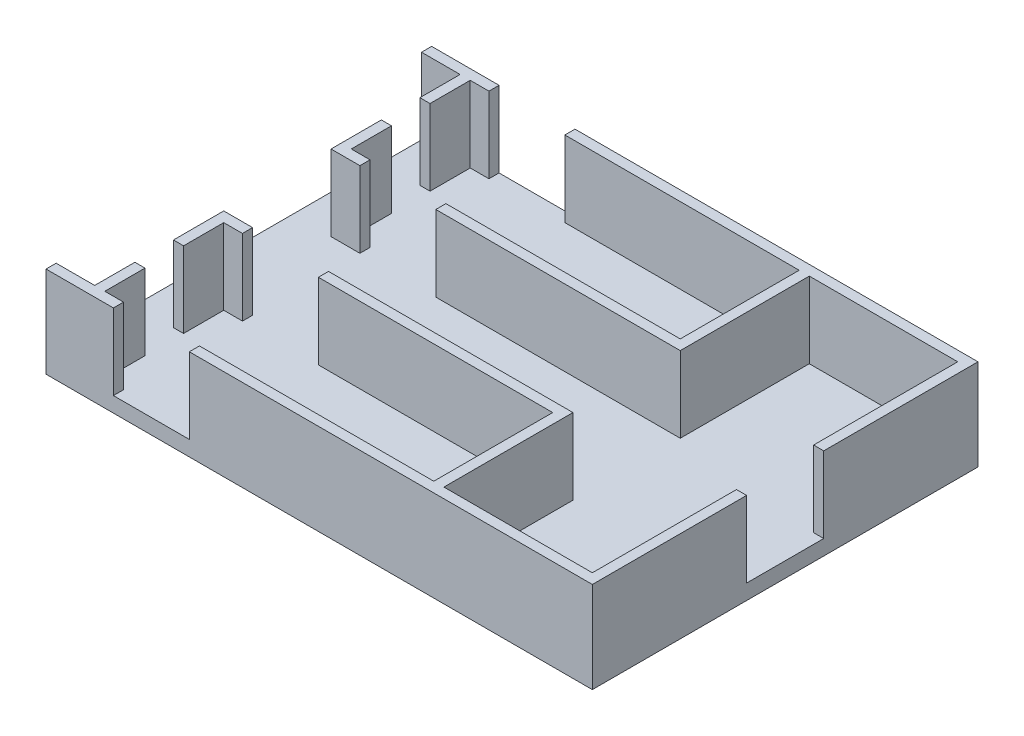
SolidWorks part; units mm, degrees
ref_plane "Front Plane" through (0, 0, 0) normal (0, 0, 1) x (1, 0, 0)
ref_plane "Top Plane" through (0, 0, 0) normal (0, 1, 0) x (1, 0, 0)
ref_plane "Right Plane" through (0, 0, 0) normal (1, 0, 0) x (0, 0, -1)
sketch "Sketch1" plane through (0, 0, 0) normal (0, 1, 0) x (1, 0, 0)
  line L1 (-53.975, 38.1) -> (53.975, 38.1)
  line L2 (-53.975, 38.1) -> (-53.975, -38.1)
  line L3 (-53.975, -38.1) -> (53.975, -38.1)
  line L4 (53.975, 38.1) -> (53.975, -38.1)
  line L5 (-53.975, 38.1) -> (53.975, -38.1) construction
  line L6 (-53.975, -38.1) -> (53.975, 38.1) construction
  point P0 (0, 0)
  dimension "D1" = 76.2
  dimension "D2" = 107.95
extrude "Boss-Extrude1" add sketch "Sketch1" along normal blind 3
sketch "Sketch2" plane through (0, 3, 0) normal (0, 1, 0) x (1, 0, 0)
  line L0 (-51.975, 36.1) -> (-53.975, 36.1)
  line L1 (-53.975, 38.1) -> (53.975, 38.1)
  line L2 (-53.975, 38.1) -> (-53.975, -38.1)
  line L3 (-53.975, -38.1) -> (53.975, -38.1)
  line L4 (53.975, 38.1) -> (53.975, -38.1)
  line L5 (-53.975, 38.1) -> (53.975, -38.1) construction
  line L6 (-53.975, -38.1) -> (53.975, 38.1) construction
  line L7 (-51.975, 36.1) -> (51.975, 36.1)
  line L8 (-51.975, 36.1) -> (-51.975, -36.1)
  line L9 (-51.975, -36.1) -> (51.975, -36.1)
  line L10 (51.975, 36.1) -> (51.975, -36.1)
  line L11 (-51.975, 36.1) -> (51.975, -36.1) construction
  line L12 (-51.975, -36.1) -> (51.975, 36.1) construction
  line L13 (-51.975, -36.1) -> (-53.975, -36.1)
  point P0 (0, 0)
  point P7 (0, 0)
  line M5 (53.975, -38.1) -> (53.975, 38.1)
  line M6 (53.975, 38.1) -> (-53.975, 38.1)
  line M7 (-53.975, 38.1) -> (-53.975, -38.1)
  line M8 (-53.975, -38.1) -> (53.975, -38.1)
  dimension "D1" = 2
  dimension "D2" = 2
extrude "Boss-Extrude2" add sketch "Sketch2" along normal blind 15 contours L9 L13 L2 L0 L7 L10 M8 M5 M6 M7 region at (-52.975, 3, -37.4213)
sketch "Sketch3" plane through (51.975, 0, 0) normal (-1, 0, 0) x (0, 0, 1)
  line L0 (36.1, 3) -> (-36.1, 3) construction
  line L1 (-7.62, 18) -> (7.62, 18)
  line L2 (-7.62, 18) -> (-7.62, 3)
  line L3 (-7.62, 3) -> (7.62, 3)
  line L4 (7.62, 18) -> (7.62, 3)
  line L5 (-7.62, 18) -> (7.62, 3) construction
  line L6 (-7.62, 3) -> (7.62, 18) construction
  line L8 (0, -1.65) -> (0, 1.65) construction
  line L9 (-36.1, 18) -> (36.1, 18) construction
  point P0 (0, 10.5)
  dimension "D1" = 7.62
extrude "Cut-Extrude1" cut sketch "Sketch3" against normal through all
sketch "Sketch4" plane through (0, 3, 0) normal (0, 1, 0) x (1, 0, 0)
  line L0 (-53.975, -36.1) -> (51.975, -36.1) construction
  line L1 (-44.355, -36.1) -> (20.645, -36.1)
  line L2 (-44.355, -36.1) -> (-44.355, -12.6)
  line L3 (-44.355, -12.6) -> (20.645, -12.6)
  line L4 (20.645, -36.1) -> (20.645, -12.6)
  line L5 (-46.355, -10.6) -> (22.645, -10.6)
  line L6 (22.645, -38.1) -> (22.645, -10.6)
  line L7 (-46.355, -38.1) -> (22.645, -38.1)
  line L8 (-46.355, -38.1) -> (-46.355, -10.6)
  line L9 (-1.65, 0) -> (1.65, 0) construction
  line L10 (-46.355, 38.1) -> (-46.355, 10.6)
  line L11 (-46.355, 38.1) -> (22.645, 38.1)
  line L12 (22.645, 38.1) -> (22.645, 10.6)
  line L13 (-46.355, 10.6) -> (22.645, 10.6)
  line L14 (20.645, 36.1) -> (20.645, 12.6)
  line L15 (-44.355, 12.6) -> (20.645, 12.6)
  line L16 (-44.355, 36.1) -> (-44.355, 12.6)
  line L17 (-44.355, 36.1) -> (20.645, 36.1)
  line L18 (-53.975, 36.1) -> (-53.975, -36.1) construction
  line L20 (-46.355, -20.54) -> (-44.355, -20.54)
  line L21 (-46.355, -28.16) -> (-44.355, -28.16)
  line L22 (-45.355, -20.54) -> (-45.355, -28.16) construction
  line L23 (-46.355, 28.16) -> (-44.355, 28.16)
  line L24 (-46.355, 20.54) -> (-44.355, 20.54)
  point P31 (-45.355, -24.35)
  point P32 (-44.355, -24.35)
  line M3 (-53.975, -36.1) -> (51.975, -36.1)
  line M9 (51.975, 36.1) -> (-53.975, 36.1)
  dimension "D1" = 23.5
  dimension "D2" = 65
  dimension "D3" = 7.62
  dimension "D5" = 7.62
  dimension "D4" = 2
extrude "Boss-Extrude4" add sketch "Sketch4" along normal up to surface (15 mm away) contours L24 L10 L13 L12 L14 L15 L16 M9 | L10 L23 L16 M9 | L21 L8 L2 M3 | L8 L20 L2 L3 L4 L6 L5 M3 region at (-45.355, 3, 32.13) region at (21.3806, 3, 24.35) region at (-45.355, 3, -32.13) region at (-45.355, 3, -19.8044) up to face at (17.325, 18, 27.2733)
sketch "Sketch5" plane through (0, 0, 36.1) normal (0, 0, -1) x (-1, 0, 0)
  line L1 (25.655, 18) -> (40.655, 18)
  line L2 (25.655, 18) -> (25.655, 3)
  line L3 (25.655, 3) -> (40.655, 3)
  line L4 (40.655, 18) -> (40.655, 3)
  line L5 (25.655, 18) -> (40.655, 3) construction
  line L6 (25.655, 3) -> (40.655, 18) construction
  line L7 (44.355, 18) -> (44.355, 3) construction
  line L8 (44.355, 18) -> (-20.645, 18) construction
  line L9 (44.355, 3) -> (-20.645, 3) construction
  point P0 (33.155, 10.5)
  dimension "D1" = 11.2
extrude "Cut-Extrude2" cut sketch "Sketch5" against normal through all and the other way through all
